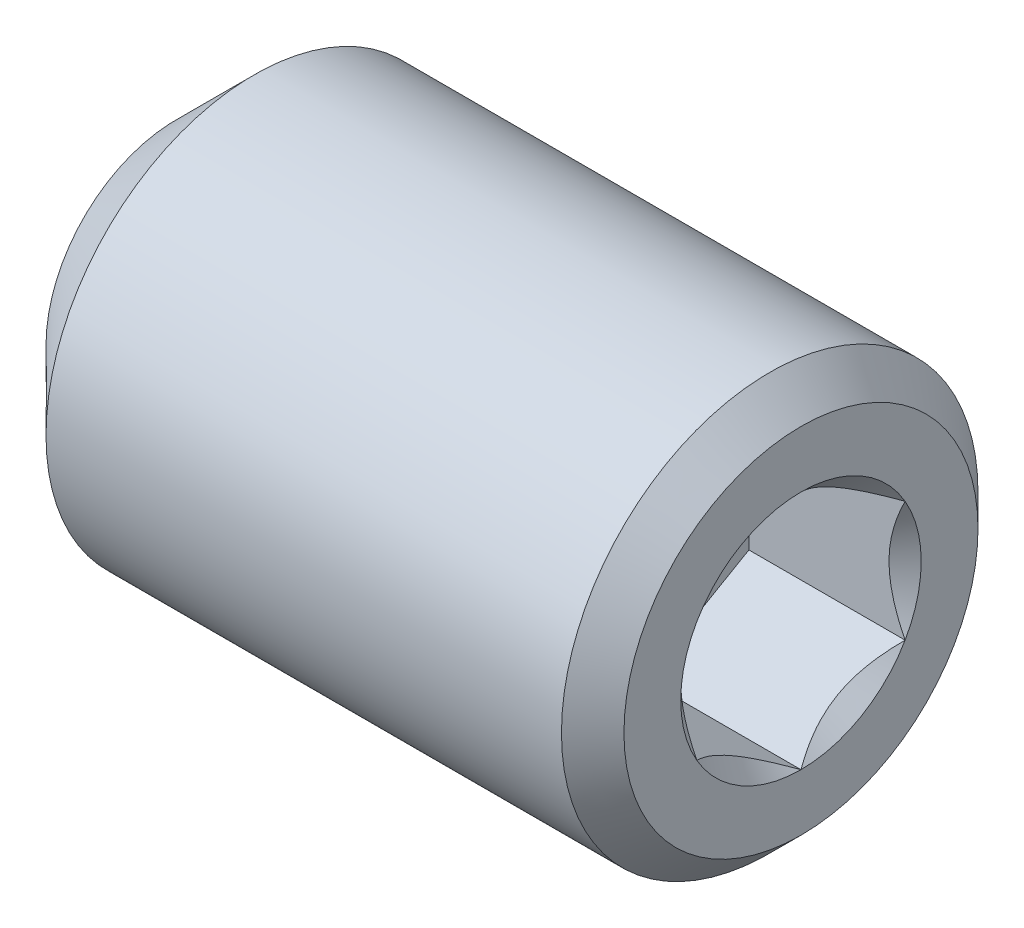
SolidWorks part; units mm, degrees
ref_plane "Front Plane" through (0, 0, 0) normal (0, 0, 1) x (1, 0, 0)
ref_plane "Top Plane" through (0, 0, 0) normal (0, 1, 0) x (1, 0, 0)
ref_plane "Right Plane" through (0, 0, 0) normal (1, 0, 0) x (0, 0, -1)
sketch "Sketch1" plane through (0, 0, 0) normal (1, 0, 0) x (0, 0, -1)
  circle A0 centre (0, 0) radius 2
  dimension "D1" = 4
extrude "Boss-Extrude1" add sketch "Sketch1" against normal blind 6
chamfer "Chamfer1" distance 0.75 angle 45 1 edges at (-6, 0, -2)
chamfer "Chamfer2" distance 0.3 angle 45 1 edges at (0, 0, -2)
sketch "Sketch2" plane through (0, 0, 0) normal (1, 0, 0) x (0, 0, -1)
  line L1 (0, 1.1547) -> (-1, 0.5774)
  line L2 (-1, 0.5774) -> (-1, -0.5774)
  line L3 (-1, -0.5774) -> (0, -1.1547)
  line L4 (0, -1.1547) -> (1, -0.5774)
  line L5 (1, -0.5774) -> (1, 0.5774)
  line L6 (1, 0.5774) -> (0, 1.1547)
  circle A0 centre (0, 0) radius 1 construction
  dimension "D1" = 2
extrude "Cut-Extrude1" cut sketch "Sketch2" against normal blind 1.5
sketch "Sketch3" plane through (0, 0, 0) normal (1, 0, 0) x (0, 0, -1)
  circle A0 centre (0, 0) radius 1.1547
extrude "Cut-Extrude2" cut sketch "Sketch3" against normal blind 1 draft 45
